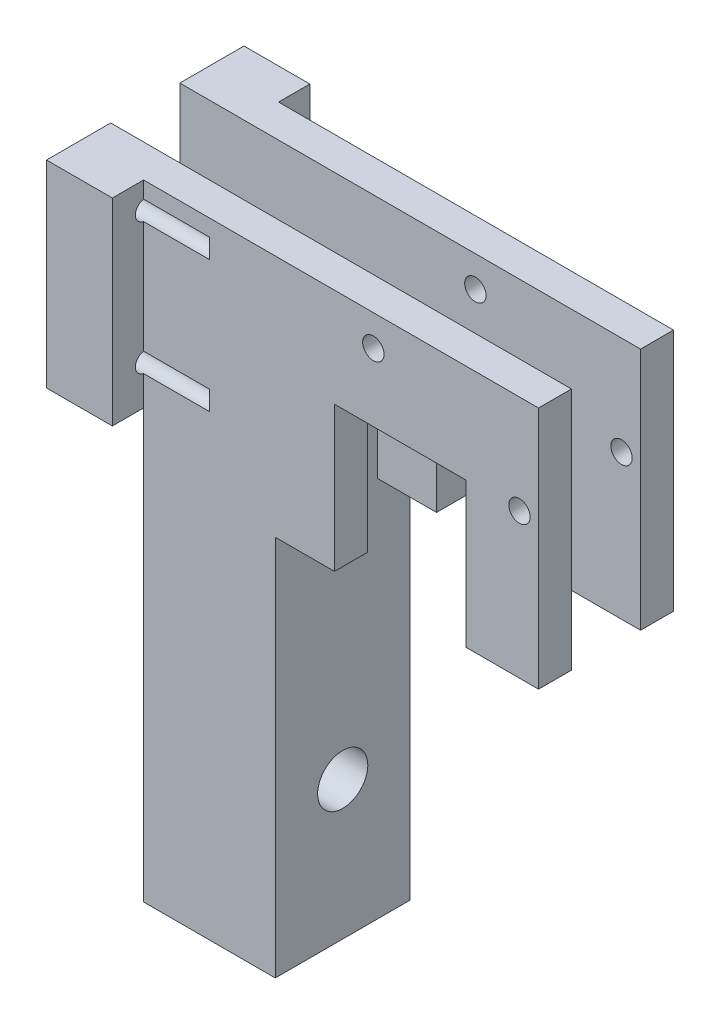
SolidWorks part; units mm, degrees
note: The reader was unsure of these and kept them because the rebuilt part matched: shared geometry of "Sketch1<3>", "Sketch1<4>", "Sketch1<5>", "Sketch1<6>", "Sketch2<3>".
ref_plane "Front Plane" through (0, 0, 0) normal (0, 0, 1) x (1, 0, 0)
ref_plane "Top Plane" through (0, 0, 0) normal (0, 1, 0) x (1, 0, 0)
ref_plane "Right Plane" through (0, 0, 0) normal (1, 0, 0) x (0, 0, -1)
sketch "Sketch1" plane through (0, 0, 0) normal (0, 0, 1) x (1, 0, 0)
  line L0 (29, 70) -> (29, 80)
  line L1 (0, 70) -> (20, 70)
  line L2 (0, 70) -> (0, 0)
  line L3 (0, 0) -> (20, 0)
  line L4 (20, 70) -> (20, 0)
  line L5 (0, 70) -> (60, 70)
  line L6 (0, 70) -> (0, 95)
  line L7 (0, 95) -> (60, 95)
  line L8 (60, 70) -> (60, 95)
  line L9 (29, 80) -> (49, 80)
  line L10 (49, 80) -> (49, 70)
  line L11 (60, 70) -> (60, 58)
  line L12 (60, 58) -> (49, 58)
  line L13 (49, 58) -> (49, 70)
  line L14 (29, 70) -> (29, 58)
  line L15 (29, 58) -> (20, 58)
  circle A0 centre (57.1, 80) radius 1.625
  circle A1 centre (34.9, 90.3) radius 1.625
  dimension "D7" = 3.25
  dimension "D1" = 70
  dimension "D2" = 60
  dimension "D3" = 22.2
  dimension "D4" = 10.3
  dimension "D5" = 10
  dimension "D6" = 2.9
  dimension "D8" = 25
  dimension "D9" = 20
  dimension "D10" = 10
  dimension "D11" = 20
  dimension "D12" = 11
  dimension "D13" = 12
extrude "Boss-Extrude1" add sketch "Sketch1" along normal blind 5 contours L4 L1 L2 L3 | L5 L8 L7 L6 L1 A1 A0
extrude "Boss-Extrude2" add sketch "Sketch1<3>" along normal blind 10.5 from surface at 5 contours L4 L1 L2 L3 starting at face at (31.6, 63, 5)
sketch "Sketch1<3>" plane through (0, 0, 0) normal (0, 0, 1) x (1, 0, 0) same geometry as "Sketch1"
extrude "Boss-Extrude3" add sketch "Sketch1<4>" along normal blind 5 from surface at 15.5 contours L4 L1 L2 L3 | L5 L8 L7 L6 L1 A1 A0
sketch "Sketch1<4>" plane through (0, 0, 0) normal (0, 0, 1) x (1, 0, 0) same geometry as "Sketch1"
extrude "Boss-Extrude4" add sketch "Sketch1<5>" along normal blind 5 contours L15 L14 L5 L4 | L13 L12 L11 L5
sketch "Sketch1<5>" plane through (0, 0, 0) normal (0, 0, 1) x (1, 0, 0) same geometry as "Sketch1"
extrude "Boss-Extrude5" add sketch "Sketch1<6>" along normal up to surface (5 mm away) from surface at 15.5 contours L15 L14 L5 L4 | L13 L12 L11 L5 up to face at (55.475, 80, 20.5) starting at face at (55.475, 80, 15.5)
sketch "Sketch1<6>" plane through (0, 0, 0) normal (0, 0, 1) x (1, 0, 0) same geometry as "Sketch1"
sketch "Sketch2" plane through (0, 0, 0) normal (1, 0, 0) x (0, 0, -1)
  line L3 (-20.5, 95) -> (-20.5, 0) construction
  line L4 (-20.5, 95) -> (-15.5, 95) construction
  line L5 (-5, 95) -> (0, 95) construction
  line L6 (4.75, 95) -> (-25.25, 95)
  line L7 (4.75, 95) -> (4.75, 65)
  line L8 (4.75, 65) -> (-25.25, 65)
  line L9 (-25.25, 95) -> (-25.25, 65)
  line L12 (-5, 95) -> (-5, 70)
  line L13 (-5, 70) -> (-15.5, 70)
  line L14 (-15.5, 70) -> (-15.5, 95)
  line L15 (-15.5, 95) -> (-5, 95)
  circle A0 centre (-0.25, 91) radius 1.5
  circle A1 centre (-20.25, 91) radius 1.5
  circle A2 centre (-20.25, 71) radius 1.5
  circle A3 centre (-0.25, 71) radius 1.5
  dimension "D1" = 3
  dimension "D2" = 20
  dimension "D3" = 20
  dimension "D4" = 0.25
  dimension "D5" = 4
  dimension "D6" = 30
  dimension "D7" = 4.75
  dimension "D8" = 30
extrude "Boss-Extrude6" add sketch "Sketch2" against normal blind 10 contours L13 L14 L6 L9 L8 L7 L12 A3 A2 A1 A0
extrude "Cut-Extrude1" cut sketch "Sketch2<3>" along normal blind 10 contours A0 | A1 | A2 | A3
sketch "Sketch2<3>" plane through (0, 0, 0) normal (1, 0, 0) x (0, 0, -1) same geometry as "Sketch2"
ref_plane "Plane1" through (-100, 0, 0) normal (-1, 0, 0) x (0, 0, 1)
sketch "Sketch3" plane through (-100, 0, 0) normal (-1, 0, 0) x (0, 0, 1)
  line L0 (20.5, 0) -> (0, 0) construction
  line L1 (20.5, 65) -> (20.5, 0) construction
  circle A0 centre (10.25, 21) radius 3.81
  point P2 (0, 0)
  dimension "D1" = 7.62
  dimension "D2" = 21
  dimension "D3" = 10.25
extrude "Cut-Extrude2" cut sketch "Sketch3" along normal up to surface (20 mm away) from surface
equation "\"D6@Sketch1\"=(28-22.2)/2"
